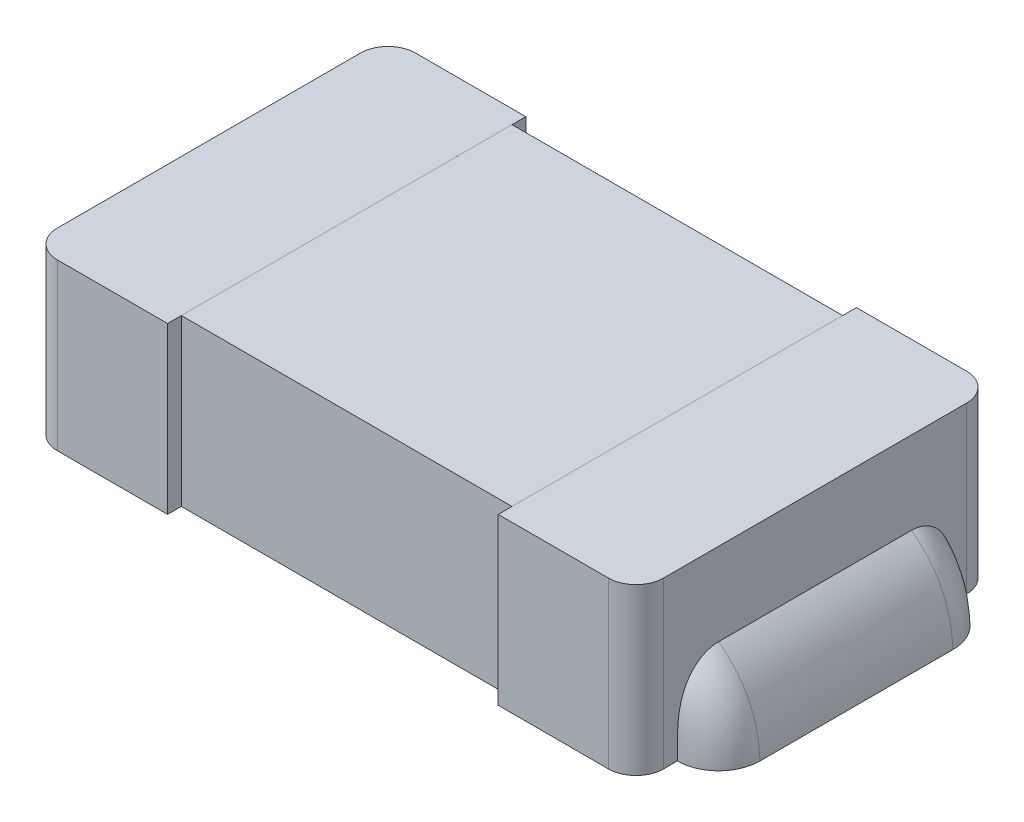
SolidWorks part; units mm, degrees
ref_plane "Front Plane" through (0, 0, 0) normal (0, 0, 1) x (1, 0, 0)
ref_plane "Top Plane" through (0, 0, 0) normal (0, 1, 0) x (1, 0, 0)
ref_plane "Right Plane" through (0, 0, 0) normal (1, 0, 0) x (0, 0, -1)
sketch "Sketch1" plane through (0, 0, 0) normal (0, 1, 0) x (1, 0, 0)
  line L1 (-1.1, -0.65) -> (1.1, -0.65)
  line L2 (-1.1, -0.65) -> (-1.1, 0.65)
  line L3 (-1.1, 0.65) -> (1.1, 0.65)
  line L4 (1.1, -0.65) -> (1.1, 0.65)
  line L5 (-1.1, -0.65) -> (1.1, 0.65) construction
  line L6 (-1.1, 0.65) -> (1.1, -0.65) construction
  point P0 (0, 0)
  dimension "D1" = 2.2
  dimension "D2" = 1.3
extrude "Boss-Extrude1" add sketch "Sketch1" along normal blind 0.6
fillet "Fillet4" radius 0.1 4 edges at (1.1, 0.3, -0.65) (1.1, 0.3, 0.65) (-1.1, 0.3, -0.65) (-1.1, 0.3, 0.65)
sketch "Sketch6" plane through (0, 0.6, 0) normal (0, 1, 0) x (1, 0, 0)
  line L0 (1, 0.65) -> (-1, 0.65) construction
  line L1 (-0.6, -0.65) -> (0.6, -0.65)
  line L2 (-0.6, -0.65) -> (-0.6, 0.65)
  line L3 (-0.6, 0.65) -> (0.6, 0.65)
  line L4 (0.6, -0.65) -> (0.6, 0.65)
  line L5 (-0.6, -0.65) -> (0.6, 0.65) construction
  line L6 (-0.6, 0.65) -> (0.6, -0.65) construction
  line L7 (-1.1, 0.55) -> (-1.1, -0.55) construction
  point P0 (0, 0)
  dimension "D1" = 0.5
extrude "Cut-Extrude2" cut sketch "Sketch6" against normal up to next
sketch "Sketch7" plane through (0, 0, 0) normal (0, 1, 0) x (1, 0, 0)
  line L0 (-0.6, 0.65) -> (-0.6, -0.65) construction
  line L1 (-0.6, 0.6) -> (0.6, 0.6)
  line L2 (-0.6, 0.6) -> (-0.6, -0.6)
  line L3 (-0.6, -0.6) -> (0.6, -0.6)
  line L4 (0.6, 0.6) -> (0.6, -0.6)
  line L5 (0.6, -0.65) -> (0.6, 0.65) construction
  line L6 (-0.6, 0.65) -> (-1, 0.65) construction
  point P8 (-0.6, 0)
  dimension "D1" = 0.05
extrude "Boss-Extrude7" add sketch "Sketch7" along normal up to surface (0.6 mm away) separate body up to face at (-0.9069, 0.6, 0)
sketch "Sketch8" plane through (0, 0, 0) normal (0, 0, 1) x (1, 0, 0)
  line L0 (-1.1, 0) -> (-1.1, 0.6) construction
  line L1 (-1.25, 0) -> (-1.1, 0)
  line L2 (-1.1, 0) -> (-1.1, 0.3)
  spline S0 degree 2 poles (-1.1, 0.3) (-1.2438, 0.1935) (-1.25, 0) knots 0 0 0 1 1 1
  dimension "D1" = 0.15
extrude "Boss-Extrude8" add sketch "Sketch8" along normal mid plane 1
fillet "Fillet5" radius 0.15 2 edges
delete or keep bodies "Body-Delete/Keep 1" type delete bodies bodies 109
mirror "Mirror2" about plane through (0, 0, 0) normal (1, 0, 0) of bodies 112
